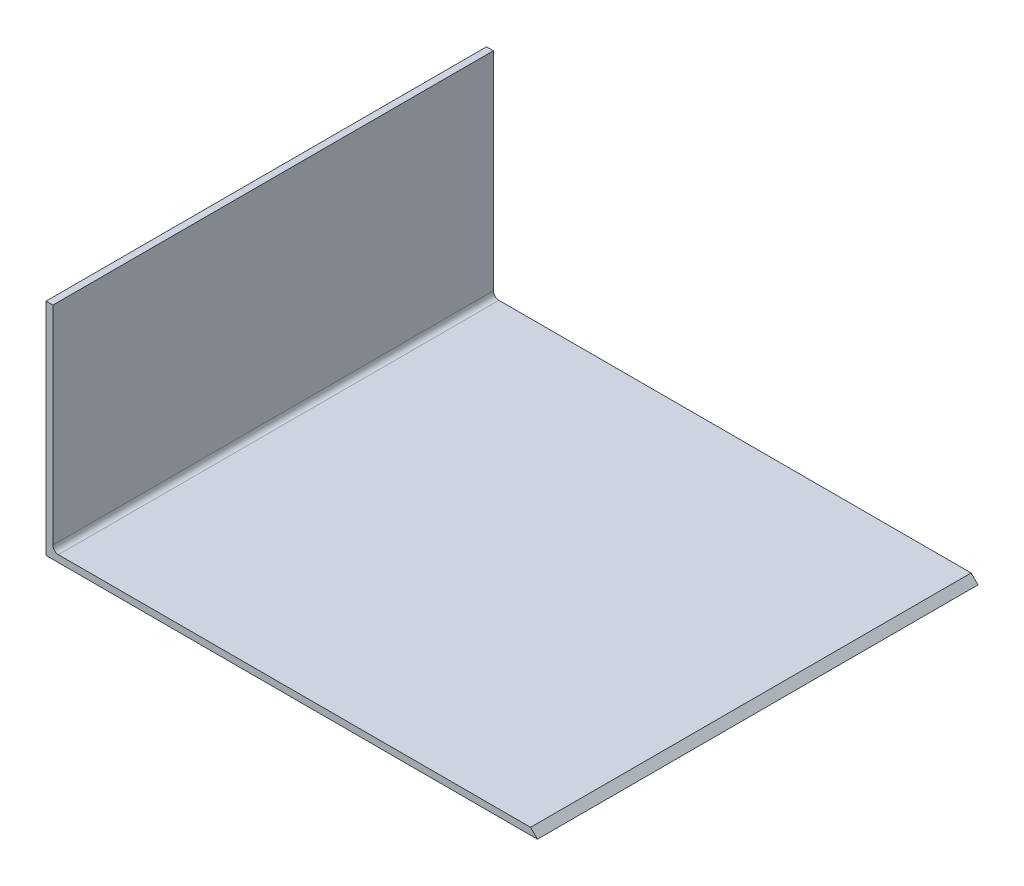
SolidWorks part; units mm, degrees
ref_plane "Front Plane" through (0, 0, 0) normal (0, 0, 1) x (1, 0, 0)
ref_plane "Top Plane" through (0, 0, 0) normal (0, 1, 0) x (1, 0, 0)
ref_plane "Right Plane" through (0, 0, 0) normal (1, 0, 0) x (0, 0, -1)
sketch "Sketch1" plane through (0, 0, 0) normal (0, 0, 1) x (1, 0, 0)
  line L1 (0, 0) -> (3.175, 0)
  line L2 (0, 0) -> (0, 98.425)
  line L3 (0, 98.425) -> (3.175, 98.425)
  line L4 (3.175, 0) -> (3.175, 98.425)
  line L5 (0, 0) -> (228.6, 0)
  line L6 (0, 0) -> (0, -3.175)
  line L7 (0, -3.175) -> (228.6, -3.175)
  line L8 (228.6, 0) -> (228.6, -3.175)
  arc A1 (3.175, 2.54) -> (5.715, 0) centre (5.715, 2.54) ccw
  dimension "D4" = 2.54
  dimension "D1" = 3.175
  dimension "D2" = 228.6
  dimension "D3" = 101.6
extrude "Boss-Extrude1" add sketch "Sketch1" along normal mid plane 203.2 contours L8 L5 L1 L6 L7 | L1 L4 L3 L2 | A1 L4 L5 region at (1.5875, 49.2125, 0) region at (114.3, -1.5875, 0) region at (3.7424, 0.5674, 0)
chamfer "Chamfer1" distance 5.08 angle 45 1 edges at (228.6, 0, 0)
ref_plane "Plane1" through (0, 0, 0) normal (0, 0, 1) x (1, 0, 0)
